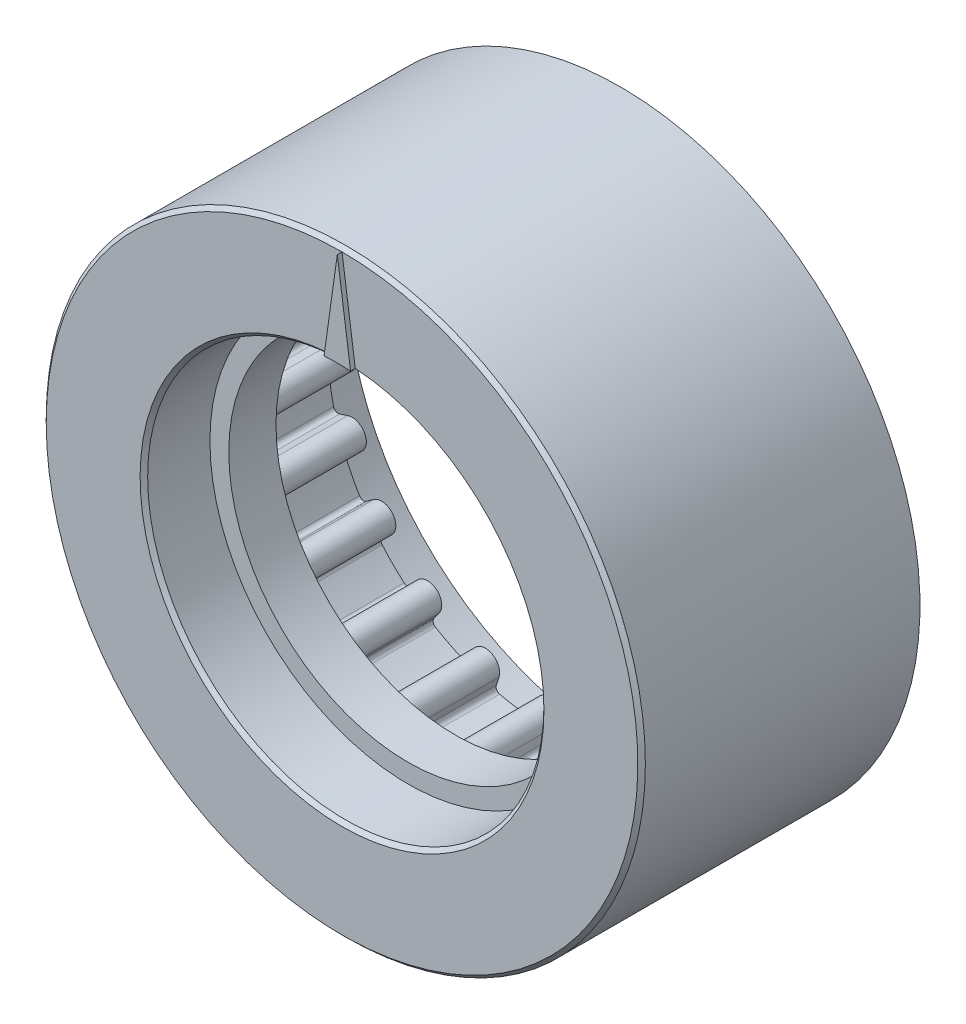
SolidWorks part; units mm, degrees
ref_plane "Ebene vorne" through (0, 0, 0) normal (0, 0, 1) x (1, 0, 0)
ref_plane "Ebene oben" through (0, 0, 0) normal (0, 1, 0) x (1, 0, 0)
ref_plane "Ebene rechts" through (0, 0, 0) normal (1, 0, 0) x (0, 0, -1)
ref_plane "Ebene1" through (0, 0, 0) normal (0, -1, 0) x (1, 0, 0)
sketch "Skizze1" plane through (0, 0, 0) normal (0, -1, 0) x (1, 0, 0)
  line L0 (31.75, 8.6) -> (0, 8.6)
  line L1 (0, 8.6) -> (0, -8.9)
  line L2 (0, -8.9) -> (31.75, -8.9)
  line L3 (31.75, -8.9) -> (31.75, 8.6)
  line L4 (0, 8.6) -> (0, -8.9) construction
  dimension "D1" = 31.75
  dimension "D2" = 17.5
revolve "Rotation1" add sketch "Skizze1" angle 360 about L4 reverse direction yes
sketch "Skizze2" plane through (0, 0, 8.6) normal (0, 0, 1) x (1, 0, 0)
  line L0 (-1.5, 22) -> (-1.5, 23.4521)
  line L1 (1.5, 22) -> (1.5, 23.4521)
  line L2 (5.3718, 21.3868) -> (5.8205, 22.7678)
  line L3 (8.225, 20.4597) -> (8.6737, 21.8407)
  line L4 (11.7178, 18.6801) -> (12.5713, 19.8548)
  line L5 (14.1448, 16.9167) -> (14.9983, 18.0915)
  line L6 (16.9167, 14.1448) -> (18.0915, 14.9983)
  line L7 (18.6801, 11.7178) -> (19.8548, 12.5713)
  line L8 (20.4597, 8.225) -> (21.8407, 8.6737)
  line L9 (21.3868, 5.3718) -> (22.7678, 5.8205)
  line L10 (22, 1.5) -> (23.4521, 1.5)
  line L11 (22, -1.5) -> (23.4521, -1.5)
  line L12 (21.3868, -5.3718) -> (22.7678, -5.8205)
  line L13 (20.4597, -8.225) -> (21.8407, -8.6737)
  line L14 (18.6801, -11.7178) -> (19.8548, -12.5713)
  line L15 (16.9167, -14.1448) -> (18.0915, -14.9983)
  line L16 (14.1448, -16.9167) -> (14.9983, -18.0915)
  line L17 (11.7178, -18.6801) -> (12.5713, -19.8548)
  line L18 (8.225, -20.4597) -> (8.6737, -21.8407)
  line L19 (5.3718, -21.3868) -> (5.8205, -22.7678)
  line L20 (1.5, -22) -> (1.5, -23.4521)
  line L21 (-1.5, -22) -> (-1.5, -23.4521)
  line L22 (-5.3718, -21.3868) -> (-5.8205, -22.7678)
  line L23 (-8.225, -20.4597) -> (-8.6737, -21.8407)
  line L24 (-11.7178, -18.6801) -> (-12.5713, -19.8548)
  line L25 (-14.1448, -16.9167) -> (-14.9983, -18.0915)
  line L26 (-16.9167, -14.1448) -> (-18.0915, -14.9983)
  line L27 (-18.6801, -11.7178) -> (-19.8548, -12.5713)
  line L28 (-20.4597, -8.225) -> (-21.8407, -8.6737)
  line L29 (-21.3868, -5.3718) -> (-22.7678, -5.8205)
  line L30 (-22, -1.5) -> (-23.4521, -1.5)
  line L31 (-22, 1.5) -> (-23.4521, 1.5)
  line L32 (-21.3868, 5.3718) -> (-22.7678, 5.8205)
  line L33 (-20.4597, 8.225) -> (-21.8407, 8.6737)
  line L34 (-18.6801, 11.7178) -> (-19.8548, 12.5713)
  line L35 (-16.9167, 14.1448) -> (-18.0915, 14.9983)
  line L36 (-14.1448, 16.9167) -> (-14.9983, 18.0915)
  line L37 (-11.7178, 18.6801) -> (-12.5713, 19.8548)
  line L38 (-8.225, 20.4597) -> (-8.6737, 21.8407)
  line L39 (-5.3718, 21.3868) -> (-5.8205, 22.7678)
  circle A0 centre (0, 22) radius 1.5
  circle A1 centre (0, 0) radius 23.5
  circle A2 centre (6.7984, 20.9232) radius 1.5
  circle A3 centre (12.9313, 17.7984) radius 1.5
  circle A4 centre (17.7984, 12.9313) radius 1.5
  circle A5 centre (20.9232, 6.7984) radius 1.5
  circle A6 centre (22, 0) radius 1.5
  circle A7 centre (20.9232, -6.7984) radius 1.5
  circle A8 centre (17.7984, -12.9313) radius 1.5
  circle A9 centre (12.9313, -17.7984) radius 1.5
  circle A10 centre (6.7984, -20.9232) radius 1.5
  circle A11 centre (0, -22) radius 1.5
  circle A12 centre (-6.7984, -20.9232) radius 1.5
  circle A13 centre (-12.9313, -17.7984) radius 1.5
  circle A14 centre (-17.7984, -12.9313) radius 1.5
  circle A15 centre (-20.9232, -6.7984) radius 1.5
  circle A16 centre (-22, 0) radius 1.5
  circle A17 centre (-20.9232, 6.7984) radius 1.5
  circle A18 centre (-17.7984, 12.9313) radius 1.5
  circle A19 centre (-12.9313, 17.7984) radius 1.5
  circle A20 centre (-6.7984, 20.9232) radius 1.5
  dimension "D1" = 3
  dimension "D3" = 20
  dimension "D2" = 22
extrude "Schnitt-Linear austragen1" cut sketch "Skizze2" against normal through all contours A20 L38 A1 L37 A19 L36 L35 A18 L34 L33 A17 L32 L31 A16 L30 L29 A15 L28 L27 A14 L26 L25 A13 L24 L23 A12 L22 L21 A11 L20 L19 A10 L18 L17 A9 L16 L15 A8 L14 region at (0, 0, 8.6)
sketch "Skizze3" plane through (0, 0, 0) normal (0, 1, 0) x (1, 0, 0)
  line L0 (29, 8.9) -> (0, 8.9)
  line L1 (0, 8.9) -> (0, 1.4)
  line L2 (0, 1.4) -> (26.5, 1.4)
  line L3 (26.5, 1.4) -> (27, 1.9)
  line L4 (27, 1.9) -> (29, 1.9)
  line L5 (29, 1.9) -> (29, 8.9)
  line L6 (0, 8.9) -> (0, 1.4) construction
  line L7 (31.75, 8.9) -> (-31.75, 8.9) construction
  dimension "D1" = 7
  dimension "D2" = 0.5
  dimension "D3" = 45
  dimension "D4" = 2
  dimension "D5" = 29
revolve "Schnitt-Rotation1" cut sketch "Skizze3" angle 360 about L6 reverse direction yes
sketch "Skizze13" plane through (0, 0, 8.6) normal (0, 0, 1) x (1, 0, 0)
  circle A1 centre (0, 0) radius 31.75
  circle A162 centre (0, 0) radius 21
  dimension "D1" = 42
extrude "Aufsatz-Linear austragen1" add sketch "Skizze13" along normal blind 12
sketch "Skizze14" plane through (0, 0, 8.6) normal (0, 0, -1) x (-1, 0, 0)
  circle A0 centre (0, 0) radius 19
  circle A1 centre (0, 0) radius 21
  dimension "D1" = 38
extrude "Aufsatz-Linear austragen2" add sketch "Skizze14" against normal offset from surface (5 mm away) 7 contours A1 A0 region at (20.406, 0, 8.6) up to face at (31.75, 0, 20.6)
fillet "Verrundung1" radius 0.5 40 edges at (-23.4521, 1.5, 3.6) (-21.8407, 8.6737, 3.6) (-22.7678, 5.8205, 3.6) (-19.8548, 12.5713, 3.6) (-23.4521, -1.5, 3.6) (-21.8407, -8.6737, 3.6) (-18.0915, -14.9983, 3.6) (-22.7678, -5.8205, 3.6) (-19.8548, -12.5713, 3.6) (-14.9983, -18.0915, 3.6) (-8.6737, -21.8407, 3.6) (-1.5, -23.4521, 3.6) (-12.5713, -19.8548, 3.6) (1.5, -23.4521, 3.6) (-5.8205, -22.7678, 3.6) (5.8205, -22.7678, 3.6) (12.5713, -19.8548, 3.6) (8.6737, -21.8407, 3.6) (14.9983, -18.0915, 3.6) (18.0915, -14.9983, 3.6) (21.8407, -8.6737, 3.6) (19.8548, -12.5713, 3.6) (22.7678, -5.8205, 3.6) (23.4521, -1.5, 3.6) (23.4521, 1.5, 3.6) (22.7678, 5.8205, 3.6) (19.8548, 12.5713, 3.6) (21.8407, 8.6737, 3.6) (18.0915, 14.9983, 3.6) (14.9983, 18.0915, 3.6) (8.6737, 21.8407, 3.6) (12.5713, 19.8548, 3.6) (5.8205, 22.7678, 3.6) (1.5, 23.4521, 3.6) (-5.8205, 22.7678, 3.6) (-1.5, 23.4521, 3.6) (-8.6737, 21.8407, 3.6) (-12.5713, 19.8548, 3.6) (-14.9983, 18.0915, 3.6) (-18.0915, 14.9983, 3.6) tangent propagation no
chamfer "Fase5" distance 0.4 angle 45 2 edges at (21, 0, 20.6) (31.75, 0, 20.6)
sketch "Sketch1" plane through (0, 0, 20.6) normal (0, 0, 1) x (1, 0, 0)
  line L0 (0, 31.35) -> (1.4049, 21.3538)
  line L1 (0, 31.35) -> (0, 21.4) construction
  line L2 (0, 31.35) -> (-1.4049, 21.3538)
  circle A0 centre (0, 0) radius 31.35 construction
  circle A1 centre (0, 0) radius 21.4 construction
  circle A2 centre (0, 0) radius 21.4
  circle M3 centre (0, 0) radius 21.4
  dimension "D1" = 8
extrude "Boss-Extrude1" add sketch "Sketch1" along normal blind 0.5 contours L0 L1 A2 | L1 L2 M3 region at (0.4679, 24.7064, 20.6) region at (-0.4679, 24.7064, 20.6)
